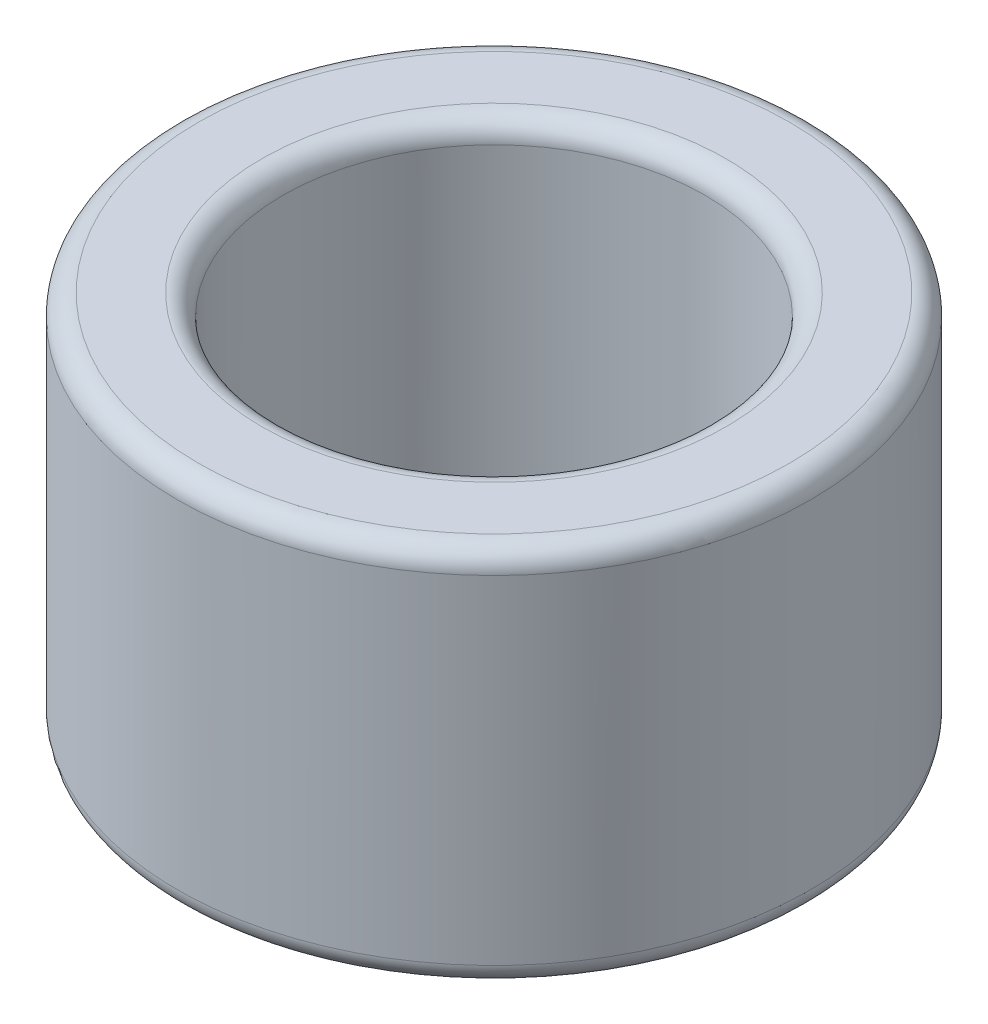
SolidWorks part; units mm, degrees
ref_plane "Front Plane" through (0, 0, 0) normal (0, 0, 1) x (1, 0, 0)
ref_plane "Top Plane" through (0, 0, 0) normal (0, 1, 0) x (1, 0, 0)
ref_plane "Right Plane" through (0, 0, 0) normal (1, 0, 0) x (0, 0, -1)
sketch "Sketch1" plane through (0, 0, 0) normal (0, 0, 1) x (1, 0, 0)
  line L2 (0, 0) -> (0, 4.5) construction
  line L4 (2.5, 0) -> (3.75, 0)
  line L5 (2.5, 0) -> (2.5, 4.5)
  line L6 (2.5, 4.5) -> (3.75, 4.5)
  line L7 (3.75, 0) -> (3.75, 4.5)
  dimension "D1" = 5
  dimension "D2" = 4.5
  dimension "D3" = 7.5
revolve "Revolve1" add sketch "Sketch1" angle 360 about L2
fillet "Fillet1" radius 0.25 4 edges at (0, 0, -2.5) (0, 0, -3.75) (0, 4.5, -3.75) (0, 4.5, -2.5)
equation "\"h\" = 4.5"
equation "\"D2@Sketch1\"=\"h\""
